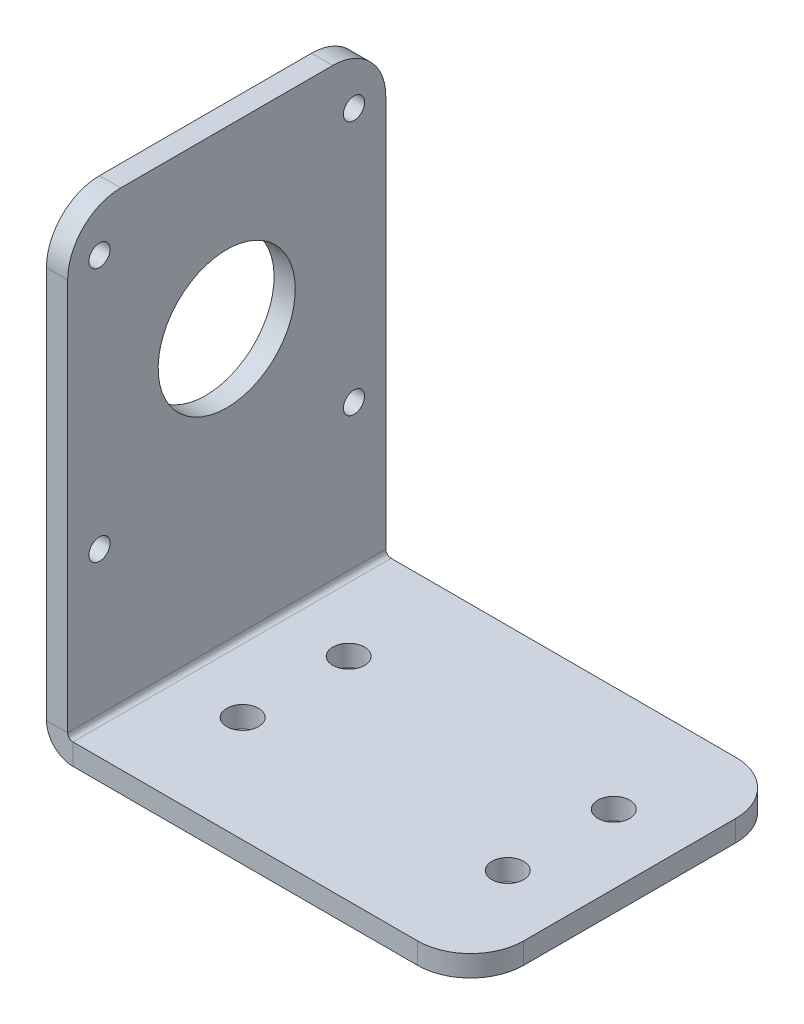
SolidWorks part; units mm, degrees
note: The reader was unsure of these and kept them because the rebuilt part matched: flange length of "Brida de arista1".
ref_plane "Alzado" through (0, 0, 0) normal (0, 0, 1) x (1, 0, 0)
ref_plane "Planta" through (0, 0, 0) normal (0, 1, 0) x (1, 0, 0)
ref_plane "Vista lateral" through (0, 0, 0) normal (1, 0, 0) x (0, 0, -1)
sketch "Croquis1" plane through (0, 0, 0) normal (0, 1, 0) x (1, 0, 0)
  line L1 (-18.75, 15) -> (18.75, 15)
  line L2 (-18.75, 15) -> (-18.75, -15)
  line L3 (-18.75, -15) -> (18.75, -15)
  line L4 (18.75, 15) -> (18.75, -15)
  line L5 (-18.75, 15) -> (18.75, -15) construction
  line L6 (-18.75, -15) -> (18.75, 15) construction
  point P0 (0, 0)
  dimension "D1" = 30
  dimension "D2" = 37.5
base flange "Brida base1" sketch "Croquis1" thickness 2 reverse thickness direction no parameters "D1"=0.7366
edge flange "Brida de arista1" sketch "Croquis8" flange angle 90 flange length 44.5 flange position bend outside bend radius 0.5 thickness 2 relief rectangular parameters "D6"=10
sketch "Croquis8" plane through (-18.75, 0, 0) normal (-1, 0, 0) x (0, 0, 1)
  line L0 (-15, 0) -> (15, 0) construction
  line L1 (-15, 0) -> (15, 0)
  line L2 (-15, 0) -> (-15, 42.5)
  line L3 (-15, 42.5) -> (15, 42.5)
  line L4 (15, 42.5) -> (15, 0)
bend "Pliegue de arista1" bend radius 0.5 bend angle 90 parameters "D5"=1
sketch "Croquis9" plane through (0, -2, 0) normal (0, -1, 0) x (1, 0, 0)
  line L0 (18.75, -15) -> (-18.75, -15) construction
  line L1 (-12.75, 5) -> (12.25, 5) construction
  line L2 (-12.75, 5) -> (-12.75, -5) construction
  line L3 (-12.75, -5) -> (12.25, -5) construction
  line L4 (12.25, 5) -> (12.25, -5) construction
  line L5 (18.75, 15) -> (18.75, -15) construction
  circle A0 centre (-12.75, 5) radius 1.5
  circle A1 centre (12.25, 5) radius 1.5
  circle A2 centre (12.25, -5) radius 1.5
  circle A3 centre (-12.75, -5) radius 1.5
  dimension "D1" = 10
  dimension "D2" = 25
  dimension "D3" = 10
  dimension "D4" = 6.5
extrude "Cortar-Extruir1" cut sketch "Croquis9" against normal blind 10 contours A0 | A1 | A2 | A3
fillet "Redondeo1" radius 5 2 edges at (18.75, -1, -15) (18.75, -1, 15)
sketch "Croquis10" plane through (-21.25, 0, 0) normal (-1, 0, 0) x (0, 0, 1)
  line L0 (-15, 42.5) -> (-15, 0.5) construction
  line L1 (15, 42.5) -> (-15, 42.5) construction
  line L3 (-12, 38) -> (12, 38) construction
  line L4 (-12, 38) -> (-12, 14) construction
  line L5 (-12, 14) -> (12, 14) construction
  line L6 (12, 38) -> (12, 14) construction
  line L7 (-12, 38) -> (12, 14) construction
  line L8 (-12, 14) -> (12, 38) construction
  circle A0 centre (0, 26) radius 6.4661
  circle A1 centre (-12, 38) radius 1
  circle A2 centre (12, 38) radius 1
  circle A3 centre (12, 14) radius 1
  circle A4 centre (-12, 14) radius 1
  dimension "D1" = 15
  dimension "D2" = 16.5
  dimension "D3" = 12
  dimension "D4" = 12
extrude "Cortar-Extruir2" cut sketch "Croquis10" against normal blind 2 normal cut yes
fillet "Redondeo2" radius 5 2 edges at (-20.25, 42.5, 15) (-20.25, 42.5, -15)
sketch "Líneas de pliegue1" [suppressed] plane through (0, 0, 0) normal (0, 1, 0) x (1, 0, 0)
sketch "Cuadro delimitador1" [suppressed] plane through (0, 0, 0) normal (0, 1, 0) x (1, 0, 0)
sheet metal parameters "Chapa metálica1" thickness 2 parameters "D1"=0.7366
flat pattern "Chapa desplegada1" [suppressed]
sketch "Líneas de pliegue2" plane through (0, 0, 0) normal (0, 1, 0) x (1, 0, 0)
sketch3d "Cuadro delimitador2" [suppressed]
  line L0 (-18.75, -15, 0) -> (18.75, -15, 0) construction
  line L1 (-18.75, 15, 0) -> (18.75, 15, 0) construction
  line L2 (-18.75, -15, 0) -> (-18.75, 15, 0) construction
  line L3 (18.75, -15, 0) -> (18.75, 15, 0) construction
sheet metal parameters "Chapa metálica2" thickness 2 parameters "D1"=0.7366
flat pattern "Chapa desplegada1"
sketch "Líneas de pliegue2" plane through (0, 0, 0) normal (0, 1, 0) x (1, 0, 0)
  line L0 (-19.9281, 15) -> (-19.9281, -15) construction
  line L1 (-19.9281, 15) -> (-19.9281, -15) construction
sketch3d "Cuadro delimitador2" [suppressed]
  line L0 (18.75, -15, 0) -> (-63.1062, -15, 0) construction
  line L1 (18.75, 15, 0) -> (-63.1062, 15, 0) construction
  line L2 (18.75, -15, 0) -> (18.75, 15, 0) construction
  line L3 (-63.1062, -15, 0) -> (-63.1062, 15, 0) construction
bend of the flat pattern "Aplanar-<Pliegue de arista1>1"
sheet metal parameters "Chapa metálica3" thickness 2 parameters "D1"=0.7366
flat pattern "Chapa desplegada1"
sketch "Líneas de pliegue2" plane through (0, 0, 0) normal (0, 1, 0) x (1, 0, 0)
  line L0 (-19.9281, 15) -> (-19.9281, -15) construction
  line L1 (-19.9281, 15) -> (-19.9281, -15) construction
sketch3d "Cuadro delimitador2" [suppressed]
  line L0 (-63.1062, -15, 0) -> (18.75, -15, 0) construction
  line L1 (-63.1062, 15, 0) -> (18.75, 15, 0) construction
  line L2 (-63.1062, -15, 0) -> (-63.1062, 15, 0) construction
  line L3 (18.75, -15, 0) -> (18.75, 15, 0) construction
bend of the flat pattern "Aplanar-<Pliegue de arista1>1"
sheet metal parameters "Chapa metálica4" thickness 2 parameters "D1"=0.7366
flat pattern "Chapa desplegada1"
sketch "Líneas de pliegue2" plane through (0, 0, 0) normal (0, 1, 0) x (1, 0, 0)
  line L0 (-19.9281, 15) -> (-19.9281, -15) construction
  line L1 (-19.9281, 15) -> (-19.9281, -15) construction
sketch3d "Cuadro delimitador2" [suppressed]
  line L0 (-63.1062, -15, 0) -> (18.75, -15, 0) construction
  line L1 (-63.1062, 15, 0) -> (18.75, 15, 0) construction
  line L2 (-63.1062, -15, 0) -> (-63.1062, 15, 0) construction
  line L3 (18.75, -15, 0) -> (18.75, 15, 0) construction
bend of the flat pattern "Aplanar-<Pliegue de arista1>1"
